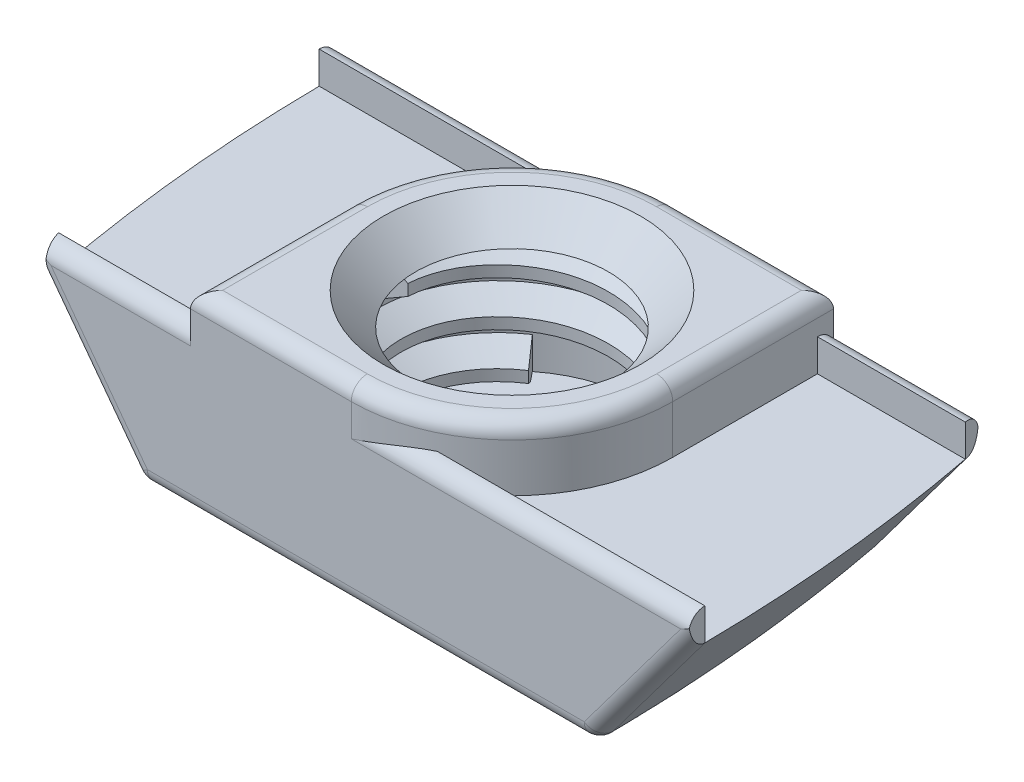
SolidWorks part; units mm, degrees
note: The reader was unsure of these and kept them because the rebuilt part matched: shared geometry of "Sketch3<3>".
material "AISI Type A2 Tool Steel"
ref_plane "Front Plane" through (0, 0, 0) normal (0, 0, 1) x (1, 0, 0)
ref_plane "Top Plane" through (0, 0, 0) normal (0, 1, 0) x (1, 0, 0)
ref_plane "Right Plane" through (0, 0, 0) normal (1, 0, 0) x (0, 0, -1)
sketch "Sketch2" plane through (0, 0, 0) normal (0, 1, 0) x (1, 0, 0)
  line L0 (0, 0) -> (7, 0)
  line L2 (-0.5, 5) -> (6.5, 5)
  arc A2 (-0.5, 5) -> (0, 0) centre (24.75, 5) ccw
  arc A3 (7, 0) -> (6.5, 5) centre (-18.25, 0) ccw
  dimension "D1" = 7
  dimension "D2" = 0.5
  dimension "D3" = 5
ref_plane "Plane1" through (0, 2, 0) normal (0, 1, 0) x (1, 0, 0)
sketch "Sketch3" plane through (0, 2, 0) normal (0, 1, 0) x (1, 0, 0)
  line L0 (-1.5, 0) -> (8.5, 0)
  line L1 (-2, 5) -> (8, 5)
  line L2 (0, 0) -> (7, 0) construction
  line L3 (-0.5, 5) -> (6.5, 5) construction
  arc A0 (-2, 5) -> (-1.5, 0) centre (23.25, 5) ccw
  arc A1 (8.5, 0) -> (8, 5) centre (-16.75, 0) ccw
  point P6 (3.5, 0)
  point P9 (3.5, 0)
  point P10 (3, 5)
  point P13 (3, 5)
  point P16 (0, 0)
  dimension "D1" = 10
loft "Loft1" add profiles "Sketch2", "Sketch3"
ref_plane "Plane2" through (0, 2.5, 0) normal (0, 1, 0) x (1, 0, 0)
sketch "Sketch4" plane through (0, 2.5, 0) normal (0, 1, 0) x (1, 0, 0)
  line L0 (-2, 5) -> (8, 5)
  line L1 (-1.5, 0) -> (8.5, 0)
  arc A0 (-2, 5) -> (-1.5, 0) centre (23.25, 5) ccw
  arc A1 (8.5, 0) -> (8, 5) centre (-16.75, 0) ccw
  point P10 (0, 0)
loft "Loft2" add profiles "Sketch4", "Sketch3<3>"
sketch "Sketch3<3>" plane through (0, 2, 0) normal (0, 1, 0) x (1, 0, 0) same geometry as "Sketch3"
ref_plane "Plane3" through (3.5, 0, 0) normal (1, 0, 0) x (0, 0, -1)
sketch "Sketch5" plane through (3.5, 0, 0) normal (1, 0, 0) x (0, 0, -1)
  line L0 (5, 2) -> (0, 2) construction
  line L1 (0, 2) -> (0.25, 2)
  line L2 (0, 2) -> (0, 2.5)
  line L3 (0, 2.5) -> (0.25, 2.5)
  line L4 (0.25, 2) -> (0.25, 2.5)
  line L5 (5, 2) -> (0, 2) construction
  line L6 (2.7541, 2.5) -> (-2.7541, 2.5) construction
  line L7 (2.7541, 2) -> (-2.7541, 2) construction
  line L8 (5, 2) -> (4.75, 2)
  line L9 (5, 2) -> (5, 2.5)
  line L10 (5, 2.5) -> (4.75, 2.5)
  line L11 (4.75, 2) -> (4.75, 2.5)
  line L12 (5, 2.5) -> (5, 2) construction
  line L14 (0.25, 2) -> (4.75, 2)
  line L15 (0.25, 2) -> (0.25, 2.5)
  line L16 (0.25, 2.5) -> (4.75, 2.5)
  line L17 (4.75, 2) -> (4.75, 2.5)
  dimension "D1" = 0.25
  dimension "D2" = 0.25
extrude "Cut-Extrude1" cut sketch "Sketch5" against normal mid plane 20 contours L16 L4 L14 L11
sketch "Sketch7" plane through (0, 2, 0) normal (0, 1, 0) x (1, 0, 0)
  line L0 (3.0252, 4.75) -> (3.4748, 0.25) construction
  line L1 (-1.9988, 4.75) -> (8.0492, 4.75) construction
  line L2 (-1.5492, 0.25) -> (8.4988, 0.25) construction
  line L3 (3.25, 5) -> (5.75, 5)
  line L4 (8, 5) -> (-2, 5) construction
  line L5 (5.75, 5) -> (5.75, 2.5)
  line L6 (5.75, 2.5) -> (3.25, 5)
  line L7 (3.25, 0) -> (0.75, 0)
  line L8 (0.75, 0) -> (0.75, 2.5)
  line L9 (0.75, 2.5) -> (3.25, 0)
  circle A0 centre (3.25, 2.5) radius 2.5
  dimension "D1" = 5
extrude "Boss-Extrude1" add sketch "Sketch7" along normal blind 1 contours L7 L8 L9 | A0 | L5 L6 L3
sketch "Sketch8" plane through (0, 3, 0) normal (0, 1, 0) x (1, 0, 0)
  circle A0 centre (3.25, 2.5) radius 2
  dimension "D1" = 4
extrude "Cut-Extrude2" cut sketch "Sketch8" against normal through all
thread "Thread1" pitch 0.7 start angle 0, offset 0.5, length 0, pitch 0.7, diameter 4
ref_plane "Plane4" through (1.25, 2.5, -2.5) normal (0, 0, 1) x (-1, 0, 0)
sketch "Thread Profile1" plane through (1.25, 2.5, -2.5) normal (0, 0, 1) x (-1, 0, 0)
  line L0 (0, 0) -> (0, 0.7) construction
  line L11 (0, 0) -> (0, 0.6125)
  line L12 (0, 0.6125) -> (-0.3789, 0.3937)
  line L13 (-0.3789, 0.3937) -> (-0.3789, 0.2187)
  line L15 (-0.3789, 0.2187) -> (0, 0)
  line L17 (-0.3789, 0.3062) -> (0, 0.3062) construction
  point P2 (0, 0)
  dimension "Pitch" = 0.7
  dimension "Profile_Angle" = 60
  dimension "Profile_Land" = 0.175
  dimension "Profile_Height" = 0.3789
sketch "Sketch11" plane through (0, 3, 0) normal (0, 1, 0) x (1, 0, 0)
  circle A0 centre (3.25, 2.5) radius 2
  circle A1 centre (3.25, 2.5) radius 1.5
  dimension "D1" = 3
extrude "Boss-Extrude2" add sketch "Sketch11" against normal blind 0.5 contours A0 | A1
sketch "Sketch12" plane through (0, 0, 0) normal (0, -1, 0) x (1, 0, 0)
  circle A0 centre (3.25, -2.5) radius 2
  circle A1 centre (3.25, -2.5) radius 1.5
  dimension "D1" = 3
extrude "Boss-Extrude3" add sketch "Sketch12" against normal blind 0.5
chamfer "Chamfer1" distance 0.5 angle 45 2 edges at (3.25, 3, -1) (3.25, 0, -4)
fillet "Fillet1" radius 0.25 4 edges
fillet "Fillet2" radius 0.25 14 edges at (2, 3, 0) (5.75, 3, -3.75) (4.5, 3, -5) (0.75, 3, -1.25) (5.0178, 3, -0.7322) (1.4822, 3, -4.2678)
